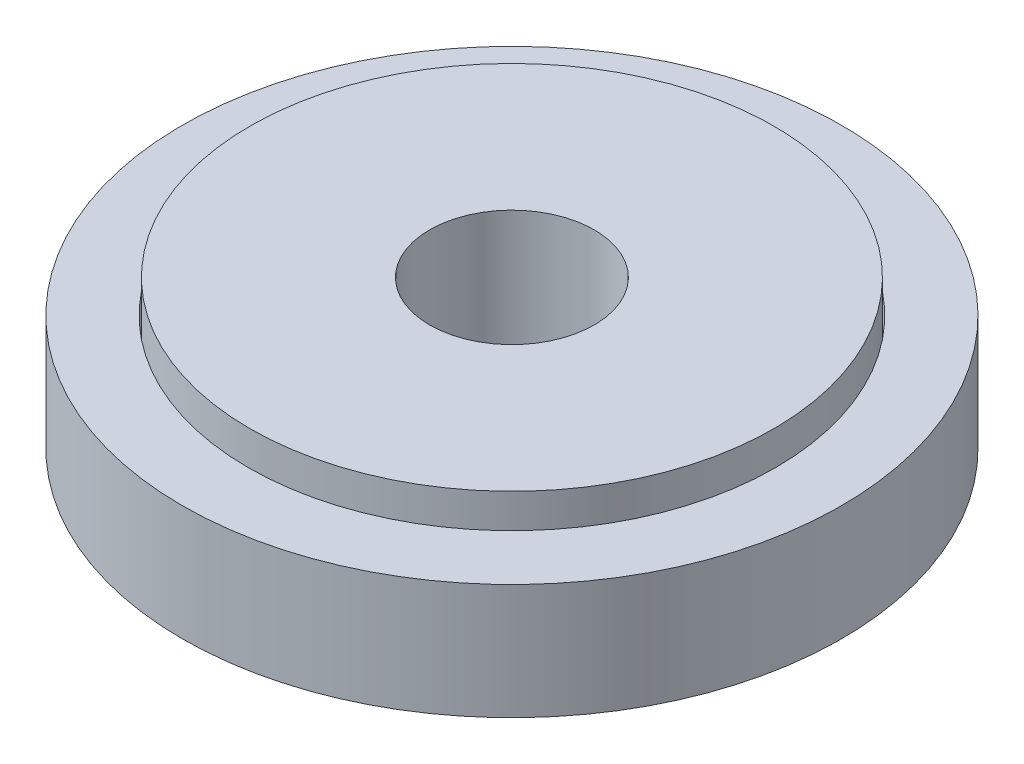
SolidWorks part; units mm, degrees
material "Rubber"
ref_plane "Front Plane" through (0, 0, 0) normal (0, 0, 1) x (1, 0, 0)
ref_plane "Top Plane" through (0, 0, 0) normal (0, 1, 0) x (1, 0, 0)
ref_plane "Right Plane" through (0, 0, 0) normal (1, 0, 0) x (0, 0, -1)
sketch "Sketch1" plane through (0, 0, 0) normal (0, 1, 0) x (1, 0, 0)
  circle A0 centre (0, 0) radius 10
  dimension "D1" = 20
extrude "Extrude-Thin1" add sketch "Sketch1" along normal blind 3.5 thin thin type one direction reverse wall 2
sketch "Sketch2" plane through (0, 3.5, 0) normal (0, 1, 0) x (1, 0, 0)
  circle A1 centre (0, 0) radius 7.95
  dimension "D1" = 15.9
extrude "Boss-Extrude1" add sketch "Sketch2" against normal through all and the other way blind 1 separate body
sketch "Sketch3" plane through (0, 4.5, 0) normal (0, 1, 0) x (1, 0, 0)
  circle A0 centre (0, 0) radius 2.5
  dimension "D1" = 5
extrude "Cut-Extrude1" cut sketch "Sketch3" against normal up to next (4.5 mm away)
